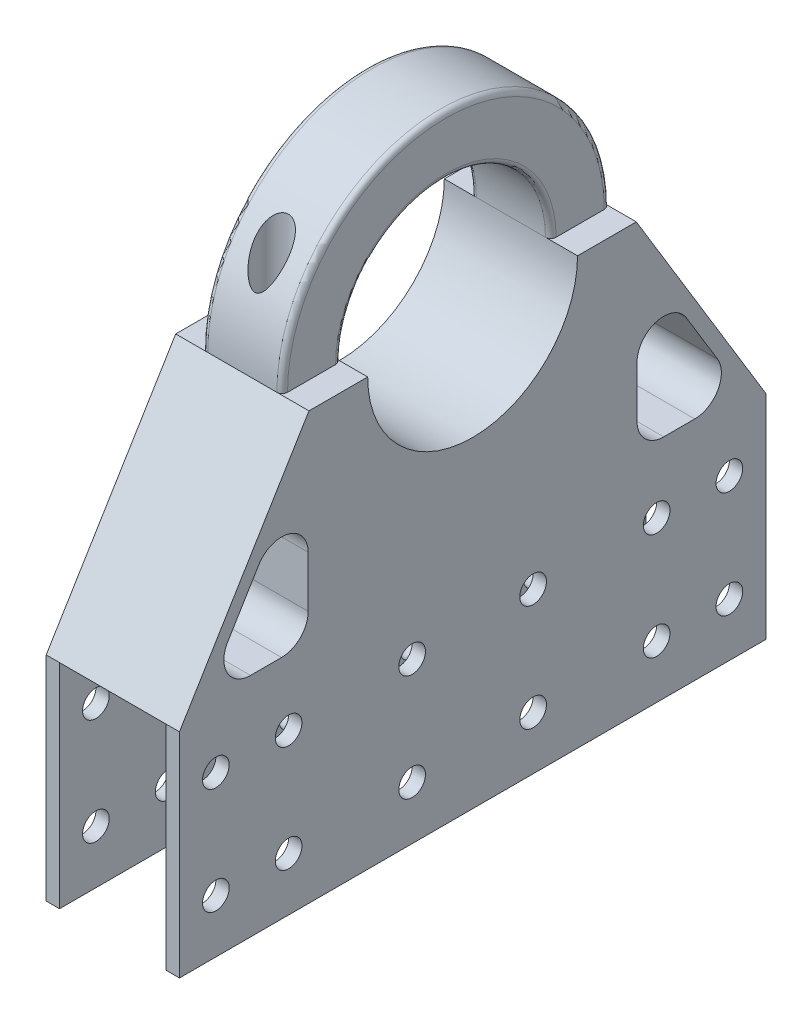
SolidWorks part; units mm, degrees
material "1060 Alloy"
ref_plane "Front Plane" through (0, 0, 0) normal (0, 0, 1) x (1, 0, 0)
ref_plane "Top Plane" through (0, 0, 0) normal (0, 1, 0) x (1, 0, 0)
ref_plane "Right Plane" through (0, 0, 0) normal (1, 0, 0) x (0, 0, -1)
sketch "Sketch1" plane through (0, 0, 0) normal (1, 0, 0) x (0, 0, -1)
  line L0 (-25, 0) -> (25, 0) construction
  line L1 (-25, 0) -> (-39, 0)
  line L2 (-39, 0) -> (-69.85, -50.8)
  line L3 (-69.85, -101.6) -> (69.85, -101.6)
  line L4 (-69.85, -101.6) -> (-69.85, -50.8)
  line L6 (69.85, -101.6) -> (69.85, -50.8)
  line L7 (25, 0) -> (39, 0)
  line L8 (39, 0) -> (69.85, -50.8)
  line L9 (-69.85, -50.8) -> (69.85, -50.8)
  line L10 (-32, 0) -> (-32, -101.6) construction
  line L11 (32, 0) -> (32, -101.6) construction
  line L12 (-35.175, 0) -> (-35.175, -101.6) construction
  line L13 (-28.825, 0) -> (-28.825, -101.6) construction
  line L14 (28.825, 0) -> (28.825, -101.6) construction
  line L15 (35.175, 0) -> (35.175, -101.6) construction
  line L16 (-69.85, -76.2) -> (-35.175, -76.2) construction
  line L17 (-69.85, -50.8) -> (-52.5125, -76.2) construction
  line L18 (-52.5125, -76.2) -> (-35.175, -50.8) construction
  line L19 (-69.85, -101.6) -> (-52.5125, -76.2) construction
  line L20 (-52.5125, -76.2) -> (-35.175, -101.6) construction
  line L21 (0, -50.8) -> (0, -101.6) construction
  line L22 (-28.825, -50.8) -> (0, -76.2) construction
  line L23 (0, -76.2) -> (28.825, -50.8) construction
  line L24 (-28.825, -101.6) -> (0, -76.2) construction
  line L25 (0, -76.2) -> (28.825, -101.6) construction
  arc A0 (-25, 0) -> (25, 0) centre (0, 0) ccw
  circle A1 centre (-61.1812, -63.5) radius 3.175
  circle A2 centre (-43.8437, -63.5) radius 3.175
  circle A3 centre (-61.1812, -88.9) radius 3.175
  circle A4 centre (-43.8437, -88.9) radius 3.175
  circle A5 centre (61.1813, -88.9) radius 3.175
  circle A6 centre (43.8438, -88.9) radius 3.175
  circle A7 centre (43.8437, -63.5) radius 3.175
  circle A8 centre (61.1812, -63.5) radius 3.175
  circle A9 centre (-14.4125, -63.5) radius 3.175
  circle A10 centre (14.4125, -63.5) radius 3.175
  circle A11 centre (-14.4125, -88.9) radius 3.175
  circle A12 centre (14.4125, -88.9) radius 3.175
  point P1 (0, -50.8)
  point P6 (0, 0)
  dimension "D1" = 50
  dimension "D11" = 6.35
  dimension "D2" = 14
  dimension "D3" = 50.8
  dimension "D4" = 139.7
  dimension "D5" = 50.8
  dimension "D6" = 14
  dimension "D7" = 3.175
  dimension "D8" = 3.175
  dimension "D9" = 3.175
  dimension "D10" = 3.175
extrude "Boss-Extrude1" add sketch "Sketch1" along normal blind 3.175 contours L9 L4 L3 L6 | A0 L1 L2 L9 L8 L7 region at (0, -31.5103, 0) region at (0, -76.2, 0)
extrude "Boss-Extrude2" add sketch "Sketch1<3>" along normal blind 25.4 from surface contours A0 L1 L2 L9 L8 L7 region at (0, -31.5103, 0) starting at face at (3.175, -88.9, -17.5875)
sketch "Sketch1<3>" plane through (0, 0, 0) normal (1, 0, 0) x (0, 0, -1) same geometry as "Sketch1"
sketch "Sketch2" plane through (0, -50.8, 0) normal (0, -1, 0) x (1, 0, 0)
  line L0 (3.175, 32) -> (28.575, 32) construction
  line L1 (3.175, -69.85) -> (3.175, 69.85) construction
  line L2 (28.575, -69.85) -> (28.575, 69.85) construction
  line L3 (28.575, 0) -> (0, 0) construction
  line L4 (28.575, 69.85) -> (28.575, -69.85) construction
  line L5 (0, 69.85) -> (0, -69.85) construction
  circle A0 centre (15.875, 32) radius 4
  circle A1 centre (15.875, -32) radius 4
  point P8 (14.6857, 31.75)
  point P17 (0, 0)
  point P18 (15.875, 32)
  dimension "D1" = 8
  dimension "D2" = 64
extrude "Cut-Extrude1" cut sketch "Sketch2" against normal through all
sketch "Sketch3" plane through (28.575, 0, 0) normal (1, 0, 0) x (0, 0, -1)
  line L0 (36, -50.8) -> (36, 0) construction
  line L1 (28, 0) -> (28, -50.8) construction
  line L2 (-28, -50.8) -> (-28, 0) construction
  line L3 (-36, 0) -> (-36, -50.8) construction
  line L4 (36, -50.8) -> (36, 0) construction
  line L5 (28, 0) -> (28, -50.8) construction
  line L6 (-28, -50.8) -> (-28, 0) construction
  line L7 (-36, 0) -> (-36, -50.8) construction
  line L8 (0, -25) -> (0, -50.8) construction
  line L9 (-69.85, -50.8) -> (-39, 0) construction
  line L10 (39.175, -47.625) -> (64.2073, -47.625)
  line L11 (-39.175, 0) -> (-39.175, -50.8) construction
  line L12 (69.85, -50.8) -> (-69.85, -50.8) construction
  line L13 (69.85, -50.8) -> (-69.85, -50.8)
  line L14 (-69.85, -50.8) -> (-39, 0)
  line L15 (39.175, -6.4049) -> (39.175, -47.625)
  line L16 (64.2073, -47.625) -> (39.175, -6.4049)
  line L17 (-39.175, -6.4049) -> (-39.175, -47.625)
  line L18 (64.2073, -47.625) -> (39.175, -47.625)
  line L19 (-64.2073, -47.625) -> (-39.175, -6.4049)
  line L20 (-39.175, -47.625) -> (-64.2073, -47.625)
  line L21 (69.85, -47.625) -> (-64.2073, -47.625) construction
  line L23 (-64.2073, -47.625) -> (-36.2862, -1.648) construction
  arc A0 (-25, 0) -> (25, 0) centre (0, 0) ccw construction
  dimension "D3" = 3.175
extrude "Cut-Extrude4" cut sketch "Sketch3" against normal through all contours L20 L17 L19 | L10 L16 L15 region at (28.575, -33.885, -47.5191) region at (28.575, -33.885, 47.5191)
fillet "Fillet1" radius 6.35 6 edges at (14.2875, -47.625, -39.175) (14.2875, -47.625, -64.2073) (14.2875, -6.4049, -39.175) (14.2875, -47.625, 64.2073) (14.2875, -47.625, 39.175) (14.2875, -6.4049, 39.175)
ref_plane "Plane1" through (15.875, 0, 0) normal (1, 0, 0) x (0, 0, -1)
sketch "Sketch4" plane through (0, 0, 0) normal (1, 0, 0) x (0, 0, -1)
  line L0 (28, 0) -> (28, -50.8) construction
  line L1 (-28, -50.8) -> (-28, 0) construction
  line L2 (28, 0) -> (28, -50.8) construction
  line L3 (-28, -50.8) -> (-28, 0) construction
  line L6 (-24.825, -47.625) -> (-24.825, -19.1453)
  line L7 (24.825, -19.1453) -> (24.825, -47.625)
  line L11 (-24.825, -50.8) -> (-24.825, 0) construction
  line L12 (69.85, -47.625) -> (-69.85, -47.625)
  line L13 (24.825, -47.625) -> (-24.825, -47.625)
  line L14 (24.825, 0) -> (24.825, -50.8) construction
  arc A2 (-31.35, 0) -> (31.35, 0) centre (0, 0) ccw
  arc A3 (-24.825, -19.1453) -> (24.825, -19.1453) centre (0, 0) ccw
  dimension "D3" = 3.175
  dimension "D1" = 6.35
  dimension "D2" = 3.175
extrude "Cut-Extrude5" [suppressed] cut sketch "Sketch4" along normal offset from surface (12.7 mm away) 3.175
fillet "Fillet2" [suppressed] radius 6.35
sketch "Sketch7" plane through (28.575, 0, 0) normal (1, 0, 0) x (0, 0, -1)
  line L0 (-69.85, -101.6) -> (-69.85, -50.8) construction
  line L1 (-69.85, -101.6) -> (69.85, -101.6) construction
  line L2 (69.85, -101.6) -> (69.85, -50.8) construction
  line L3 (58.3494, -37.9789) -> (50.9526, -25.7988) construction
  line L4 (45.525, -47.625) -> (52.9218, -47.625) construction
  line L5 (39.175, -29.0948) -> (39.175, -41.275) construction
  line L6 (-45.525, -47.625) -> (-52.9218, -47.625) construction
  line L7 (-58.3494, -37.9789) -> (-50.9526, -25.7988) construction
  line L8 (-39.175, -29.0948) -> (-39.175, -41.275) construction
  line L9 (69.85, -50.8) -> (39, 0) construction
  line L10 (39, 0) -> (25, 0) construction
  line L11 (-39, 0) -> (-25, 0) construction
  line L12 (-69.85, -50.8) -> (-39, 0) construction
  line L13 (-69.85, -101.6) -> (-69.85, -50.8)
  line L14 (-69.85, -101.6) -> (69.85, -101.6)
  line L15 (69.85, -101.6) -> (69.85, -50.8)
  line L16 (58.3494, -37.9789) -> (50.9526, -25.7988)
  line L17 (45.525, -47.625) -> (52.9218, -47.625)
  line L18 (39.175, -29.0948) -> (39.175, -41.275)
  line L19 (-45.525, -47.625) -> (-52.9218, -47.625)
  line L20 (-58.3494, -37.9789) -> (-50.9526, -25.7988)
  line L21 (-39.175, -29.0948) -> (-39.175, -41.275)
  line L22 (69.85, -50.8) -> (39, 0)
  line L23 (39, 0) -> (25, 0)
  line L24 (-39, 0) -> (-25, 0)
  line L25 (-69.85, -50.8) -> (-39, 0)
  circle A0 centre (-43.8437, -88.9) radius 3.175 construction
  circle A1 centre (-61.1812, -88.9) radius 3.175 construction
  circle A2 centre (-61.1812, -63.5) radius 3.175 construction
  circle A3 centre (-43.8437, -63.5) radius 3.175 construction
  circle A4 centre (14.4125, -88.9) radius 3.175 construction
  circle A5 centre (-14.4125, -88.9) radius 3.175 construction
  circle A6 centre (-14.4125, -63.5) radius 3.175 construction
  circle A7 centre (14.4125, -63.5) radius 3.175 construction
  circle A8 centre (61.1813, -88.9) radius 3.175 construction
  circle A9 centre (43.8438, -88.9) radius 3.175 construction
  circle A10 centre (43.8437, -63.5) radius 3.175 construction
  circle A11 centre (61.1812, -63.5) radius 3.175 construction
  arc A12 (52.9218, -47.625) -> (58.3494, -37.9789) centre (52.9218, -41.275) ccw construction
  arc A13 (39.175, -41.275) -> (45.525, -47.625) centre (45.525, -41.275) ccw construction
  arc A14 (50.9526, -25.7988) -> (39.175, -29.0948) centre (45.525, -29.0948) ccw construction
  arc A15 (-58.3494, -37.9789) -> (-52.9218, -47.625) centre (-52.9218, -41.275) ccw construction
  arc A16 (-45.525, -47.625) -> (-39.175, -41.275) centre (-45.525, -41.275) ccw construction
  arc A17 (-39.175, -29.0948) -> (-50.9526, -25.7988) centre (-45.525, -29.0948) ccw construction
  arc A18 (-25, 0) -> (25, 0) centre (0, 0) ccw construction
  circle A19 centre (-43.8437, -88.9) radius 3.175
  circle A20 centre (-61.1812, -88.9) radius 3.175
  circle A21 centre (-61.1812, -63.5) radius 3.175
  circle A22 centre (-43.8437, -63.5) radius 3.175
  circle A23 centre (14.4125, -88.9) radius 3.175
  circle A24 centre (-14.4125, -88.9) radius 3.175
  circle A25 centre (-14.4125, -63.5) radius 3.175
  circle A26 centre (14.4125, -63.5) radius 3.175
  circle A27 centre (61.1813, -88.9) radius 3.175
  circle A28 centre (43.8438, -88.9) radius 3.175
  circle A29 centre (43.8437, -63.5) radius 3.175
  circle A30 centre (61.1812, -63.5) radius 3.175
  arc A31 (52.9218, -47.625) -> (58.3494, -37.9789) centre (52.9218, -41.275) ccw
  arc A32 (39.175, -41.275) -> (45.525, -47.625) centre (45.525, -41.275) ccw
  arc A33 (50.9526, -25.7988) -> (39.175, -29.0948) centre (45.525, -29.0948) ccw
  arc A34 (-58.3494, -37.9789) -> (-52.9218, -47.625) centre (-52.9218, -41.275) ccw
  arc A35 (-45.525, -47.625) -> (-39.175, -41.275) centre (-45.525, -41.275) ccw
  arc A36 (-39.175, -29.0948) -> (-50.9526, -25.7988) centre (-45.525, -29.0948) ccw
  arc A37 (-25, 0) -> (25, 0) centre (0, 0) ccw
extrude "Boss-Extrude3" add sketch "Sketch7" along normal blind 3.175
sketch "Sketch8" [suppressed] plane through (31.75, 0, 0) normal (1, 0, 0) x (0, 0, -1)
  line L0 (24.825, -41.275) -> (24.825, -32.8628) construction
  line L1 (-18.475, -47.625) -> (18.475, -47.625) construction
  line L2 (-24.825, -32.8628) -> (-24.825, -41.275) construction
  line L3 (24.825, -41.275) -> (24.825, -32.8628)
  line L4 (-18.475, -47.625) -> (18.475, -47.625)
  line L5 (-24.825, -32.8628) -> (-24.825, -41.275)
  line L7 (-69.85, -101.6) -> (69.85, -101.6)
  line L8 (69.85, -101.6) -> (69.85, -50.8)
  line L9 (69.85, -50.8) -> (37.7, 0)
  line L10 (37.7, 0) -> (25, 0)
  line L11 (-25, 0) -> (-37.7, 0)
  line L12 (-37.7, 0) -> (-69.85, -50.8)
  line L13 (-69.85, -50.8) -> (-69.85, -101.6)
  line L14 (-69.85, -101.6) -> (69.85, -101.6)
  line L15 (69.85, -101.6) -> (69.85, -50.8)
  line L16 (69.85, -50.8) -> (37.7, 0)
  line L17 (37.7, 0) -> (25, 0)
  line L18 (-25, 0) -> (-37.7, 0)
  line L19 (-37.7, 0) -> (-69.85, -50.8)
  line L20 (-69.85, -50.8) -> (-69.85, -101.6)
  arc A0 (24.825, -32.8628) -> (15.3632, -27.3276) centre (18.475, -32.8628) ccw construction
  arc A1 (-25, 0) -> (25, 0) centre (0, 0) ccw
  arc A2 (-25, 0) -> (25, 0) centre (0, 0) ccw
  arc A3 (18.475, -47.625) -> (24.825, -41.275) centre (18.475, -41.275) ccw construction
  arc A4 (-24.825, -41.275) -> (-18.475, -47.625) centre (-18.475, -41.275) ccw construction
  arc A5 (-15.3632, -27.3276) -> (-24.825, -32.8628) centre (-18.475, -32.8628) ccw construction
  arc A6 (-15.3632, -27.3276) -> (15.3632, -27.3276) centre (0, 0) ccw construction
  arc A7 (24.825, -32.8628) -> (15.3632, -27.3276) centre (18.475, -32.8628) ccw
  arc A8 (18.475, -47.625) -> (24.825, -41.275) centre (18.475, -41.275) ccw
  arc A9 (-24.825, -41.275) -> (-18.475, -47.625) centre (-18.475, -41.275) ccw
  arc A10 (-15.3632, -27.3276) -> (-24.825, -32.8628) centre (-18.475, -32.8628) ccw
  arc A11 (-15.3632, -27.3276) -> (15.3632, -27.3276) centre (0, 0) ccw
  dimension "D1" = 0
extrude "Cut-Extrude7" [suppressed] cut sketch "Sketch8" against normal offset from surface (12.7 mm away) 3.175 contours A7 A11 A10 L5 A9 L4 A8 L3
sketch "Sketch9" plane through (0, 0, 0) normal (-1, 0, 0) x (0, 0, 1)
  line L0 (-39, 0) -> (-25, 0)
  line L1 (25, 0) -> (39, 0)
  arc A0 (-25, 0) -> (25, 0) centre (0, 0) cw
  arc A1 (-25, 0) -> (25, 0) centre (0, 0) ccw construction
  arc A2 (-39, 0) -> (39, 0) centre (0, 0) cw
  dimension "D1" = 39
extrude "Boss-Extrude4" add sketch "Sketch9" along normal mid plane 19 from surface separate body starting at plane "Plane1"
sketch "Sketch10" plane through (0, 0, 0) normal (0, 1, 0) x (1, 0, 0)
  circle A0 centre (15.875, 32) radius 4 construction
  circle A1 centre (15.875, -32) radius 4 construction
  circle A2 centre (15.875, 32) radius 4
  circle A3 centre (15.875, -32) radius 4
extrude "Cut-Extrude8" cut sketch "Sketch10" along normal through all
fillet "Fillet3" radius 1.27 4 edges at (6.375, 25, 0) (6.375, 39, 0) (25.375, 25, 0) (25.375, 39, 0)
